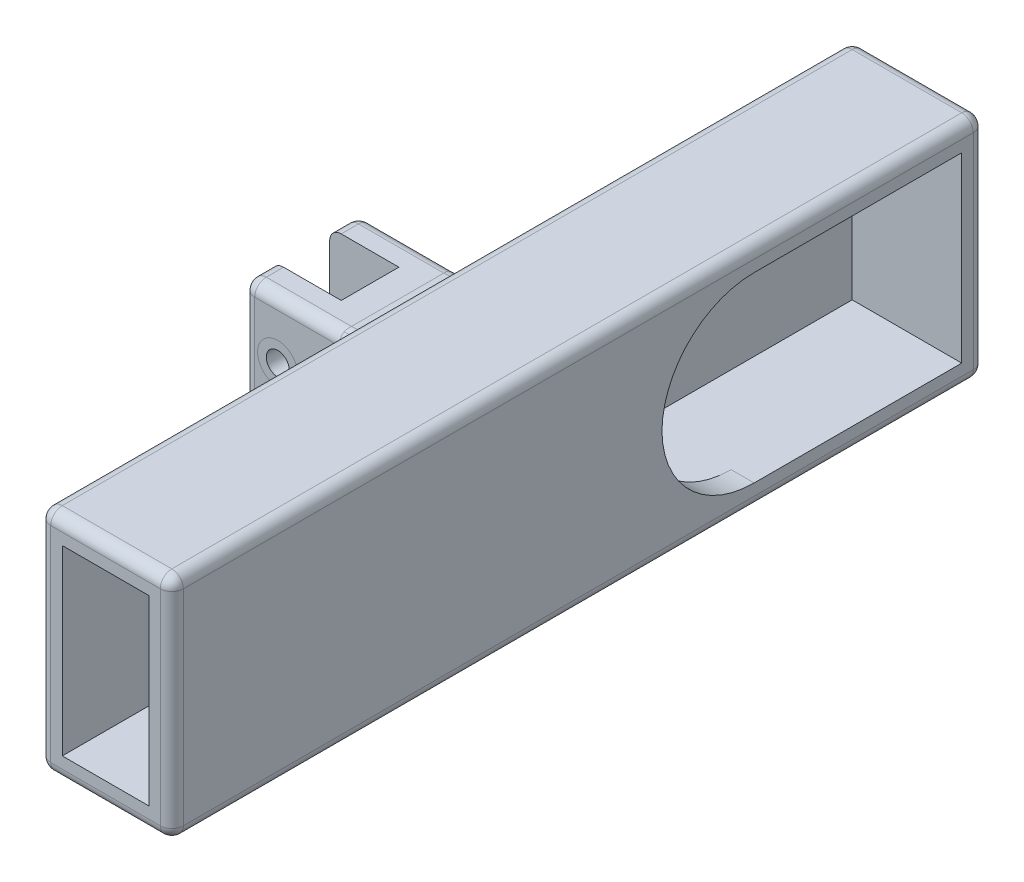
SolidWorks part; units mm, degrees
ref_plane "Alzado" through (0, 0, 0) normal (1, 0, 0) x (0, 1, 0)
ref_plane "Planta" through (0, 0, 0) normal (0, 0, 1) x (0, 1, 0)
ref_plane "Vista lateral" through (0, 0, 0) normal (0, 1, 0) x (-1, 0, 0)
sketch "Croquis1" plane through (0, 0, 0) normal (0, 0, 1) x (0, 1, 0)
  line L1 (-9.9, -5.75) -> (9.9, -5.75)
  line L2 (-9.9, -5.75) -> (-9.9, 5.75)
  line L3 (-9.9, 5.75) -> (9.9, 5.75)
  line L4 (9.9, -5.75) -> (9.9, 5.75)
  line L5 (-9.9, -5.75) -> (9.9, 5.75) construction
  line L6 (-9.9, 5.75) -> (9.9, -5.75) construction
  point P0 (0, 0)
  dimension "D1" = 19.8
  dimension "D2" = 11.5
extrude "Saliente-Extruir1" add sketch "Croquis1" along normal blind 70.5 contours L2 L1 L4 L3
shell "Vaciado1" thickness 2 removed face at (0, 0, 70.5)
sketch "Croquis6" plane through (-5.75, 0, 29.1749) normal (-1, 0, 0) x (0, -1, 0)
  line L0 (-4.9, 0.3251) -> (4.9, 0.3251)
  line L1 (-4.9, 0.3251) -> (-4.9, 10.3251)
  line L2 (4.9, 0.3251) -> (4.9, 10.3251)
  line L3 (-4.9, 10.3251) -> (4.9, 10.3251)
  line L4 (9.9, 41.3251) -> (-9.9, 41.3251) construction
  line L7 (9.9, -29.1749) -> (-9.9, -29.1749) construction
  line L9 (-9.9, 41.3251) -> (-9.9, -29.1749) construction
  line L10 (9.9, 41.3251) -> (9.9, -29.1749) construction
  dimension "D1" = 10
  dimension "D2" = 31
  dimension "D3" = 29.5
  dimension "D4" = 5
  dimension "D5" = 5
  dimension "D6" = 9.8
extrude "Saliente-Extruir4" add sketch "Croquis6" along normal blind 13.3098
sketch "Croquis8" plane through (0, 0, 39.5) normal (0, 0, 1) x (1, 0, 0)
  line L0 (-19.0598, -4.9) -> (-19.0598, 4.9) construction
  line L2 (-19.0598, 4.9) -> (-5.75, 4.9) construction
  circle A0 centre (-16.0598, -0.1) radius 1
  circle A1 centre (-16.0598, -9.9) radius 1
  dimension "D4" = 2
  dimension "D5" = 2
  dimension "D1" = 3
  dimension "D2" = 3
  dimension "D3" = 9.8
  dimension "D6" = 5
extrude "Cortar-Extruir3" cut sketch "Croquis8" against normal blind 10 contours A0 | A1 region at (-16.0598, -0.1, 39.5)
sketch "Croquis11" plane through (5.75, 0, 0) normal (1, 0, 0) x (0, 1, 0)
  line L2 (-7.9, 2) -> (7.9, 2)
  line L6 (7.9, 2) -> (7.9, 28)
  line L7 (-7.9, 2) -> (-7.9, 28)
  line L8 (-7.9, 28) -> (7.9, 28)
extrude "Cortar-Extruir5" cut sketch "Croquis11" against normal blind 2
fillet "Redondeo2" radius 8 2 edges at (4.75, -7.9, 28) (4.75, 7.9, 28)
fillet "Redondeo6" radius 1 20 edges at (5.75, 9.9, 35.25) (-12.4049, 4.9, 39.5) (5.75, -9.9, 35.25) (-12.4049, -4.9, 39.5) (0, 9.9, 70.5) (0, -9.9, 70.5) (5.75, 0, 70.5) (5.75, 0, 0) (-19.0598, 0, 39.5) (-19.0598, -4.9, 34.5) (-19.0598, 0, 29.5) (-19.0598, 4.9, 34.5) (-5.75, 0, 0) (-5.75, -9.9, 35.25) (-12.4049, -4.9, 29.5) (-12.4049, 4.9, 29.5) (-5.75, 0, 70.5) (0, -9.9, 0) (0, 9.9, 0) (-5.75, 9.9, 35.25)
sketch "Croquis12" plane through (0, 9.9, 0) normal (0, 1, 0) x (-1, 0, 0)
sketch "Croquis14" plane through (-19.0598, 0, 0) normal (-1, 0, 0) x (0, -1, 0)
  line L0 (-4.9, 34.5) -> (-4.9, 37)
  line L2 (-4.9, 37) -> (4.9, 37)
  line L4 (4.9, 37) -> (4.9, 32)
  line L5 (4.9, 32) -> (-4.9, 32)
  line L6 (-4.9, 32) -> (-4.9, 34.5)
  line L7 (3.9, 38.5) -> (-3.9, 38.5) construction
  line L9 (-3.9, 30.5) -> (3.9, 30.5) construction
  line L10 (4.9, 30.5) -> (4.9, 38.5) construction
  line L11 (-4.9, 38.5) -> (-4.9, 30.5) construction
  dimension "D1" = 1.5
  dimension "D2" = 5
  dimension "D3" = 1.5
extrude "Cortar-Extruir6" cut sketch "Croquis14" against normal blind 6
fillet "Redondeo9" radius 5 8 edges at (-5.75, 0, 29.5) (-5.75, 0, 39.5) (-5.75, -4.6071, 39.2071) (-5.75, -4.9, 34.5) (-5.75, -4.6071, 29.7929) (-5.75, 4.6071, 29.7929) (-5.75, 4.9, 34.5) (-5.75, 4.6071, 39.2071)
sketch "Croquis15" plane through (0, 0, 39.5) normal (0, 0, 1) x (1, 0, 0)
  circle A0 centre (-16.0598, -0.1) radius 1.75
  dimension "D1" = 3.5
split line "Línea de partición1"
equation "\"15.8mm.\"=19.8"
